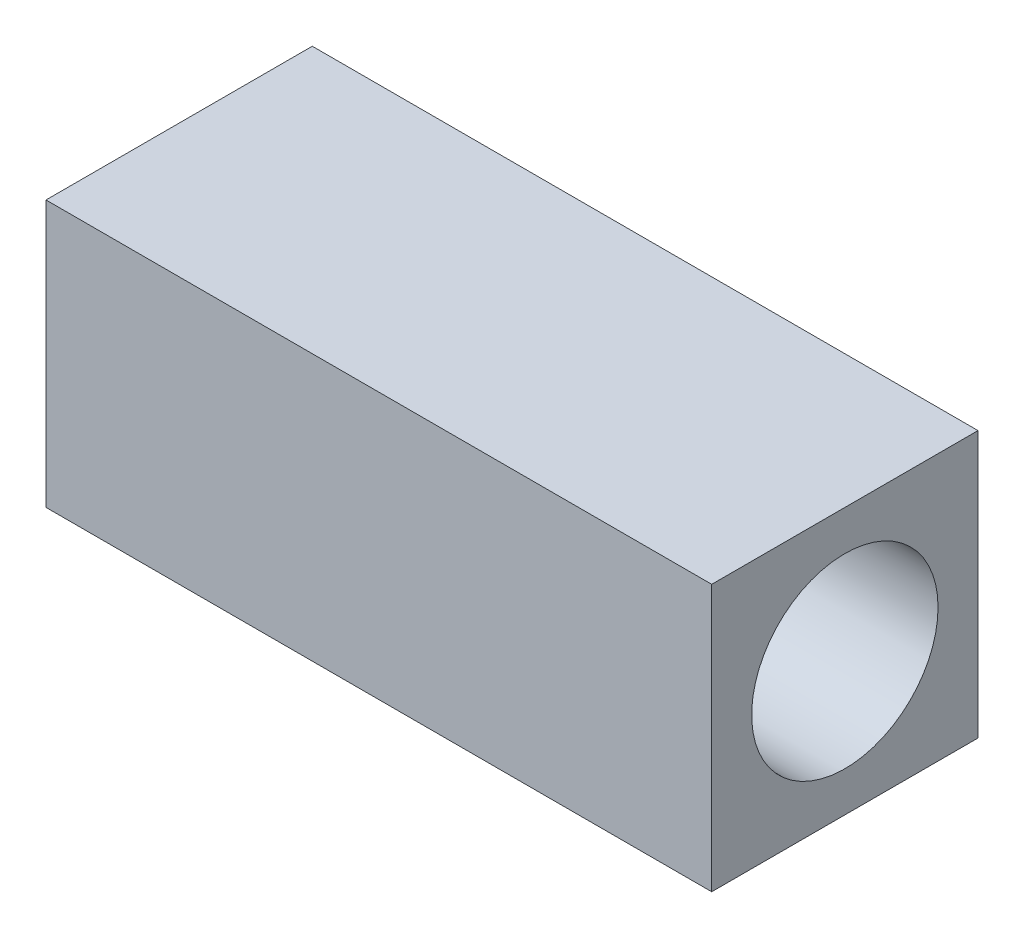
SolidWorks part; units mm, degrees
ref_plane "Alzado" through (0, 0, 0) normal (0, 0, 1) x (1, 0, 0)
ref_plane "Planta" through (0, 0, 0) normal (0, 1, 0) x (1, 0, 0)
ref_plane "Vista lateral" through (0, 0, 0) normal (1, 0, 0) x (0, 0, -1)
sketch "Croquis1" plane through (0, 0, 0) normal (0, 0, 1) x (1, 0, 0)
  line L1 (0, 0) -> (1000, 0)
  line L2 (0, 0) -> (0, 400)
  line L3 (0, 400) -> (1000, 400)
  line L4 (1000, 0) -> (1000, 400)
  dimension "D1" = 400
  dimension "D2" = 1000
extrude "Saliente-Extruir1" add sketch "Croquis1" along normal blind 400
sketch "Croquis2" plane through (1000, 0, 0) normal (1, 0, 0) x (0, 0, -1)
  line L0 (-400, 0) -> (-400, 400) construction
  line L1 (-400, 400) -> (0, 400) construction
  circle A0 centre (-200, 200) radius 140
  point P4 (0, 0)
  point P5 (0, 0)
  point P6 (0, 0)
  dimension "D1" = 200
  dimension "D2" = 200
extrude "Cortar-Extruir1" cut sketch "Croquis2" against normal blind 1000 contours A0
